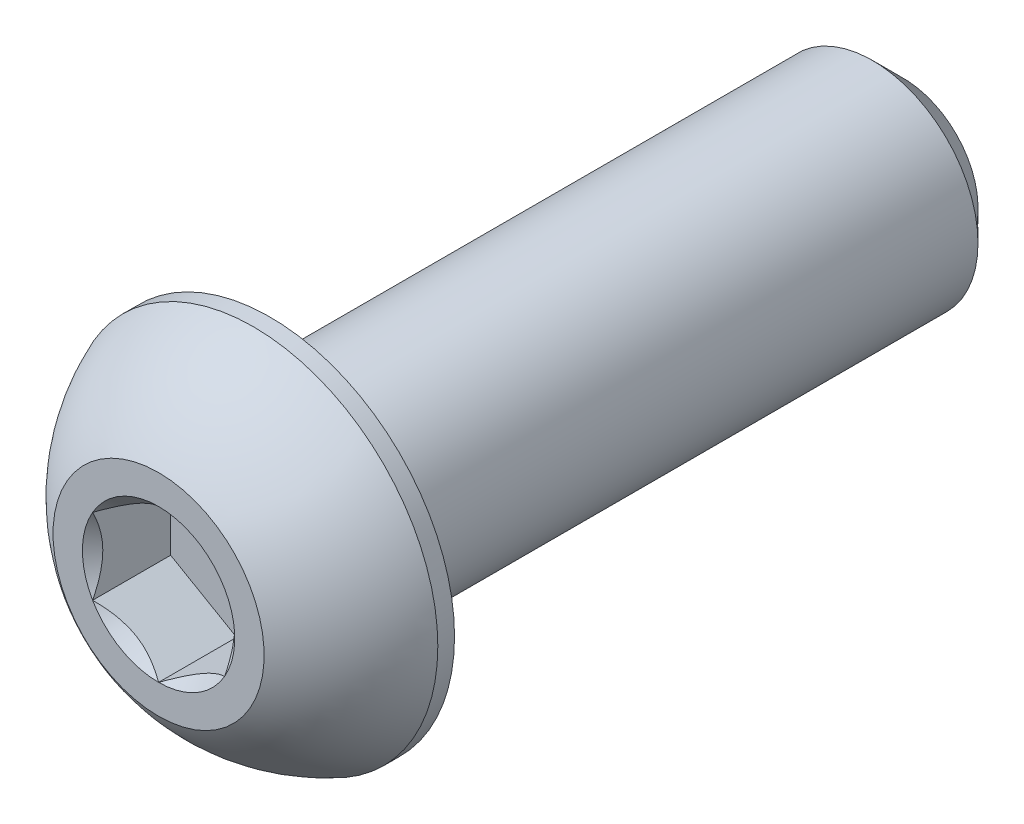
SolidWorks part; units mm, degrees
ref_plane "Front" through (0, 0, 0) normal (0, 0, 1) x (1, 0, 0)
ref_plane "Top" through (0, 0, 0) normal (0, 1, 0) x (1, 0, 0)
ref_plane "Right" through (0, 0, 0) normal (1, 0, 0) x (0, 0, -1)
sketch "Sketch1" plane through (0, 0, 0) normal (1, 0, 0) x (0, 0, -1)
  line L2 (3.3528, 3.175) -> (22.4028, 3.175)
  line L3 (22.4028, 3.175) -> (22.4028, 0)
  line L4 (22.4028, 0) -> (3.3528, 0)
  line L6 (2.8499, 5.5499) -> (3.3528, 5.5499) construction
  line L7 (22.4028, 3.175) -> (22.4028, -3.175) construction
  line L8 (0, 0) -> (3.3528, 0) construction
  line L9 (3.3528, 5.5499) -> (3.3528, -5.5499) construction
  line L11 (3.3528, 3.175) -> (3.3528, 0)
  line L13 (0, 1.9844) -> (0, -1.9844) construction
  line L14 (0, 1.9844) -> (0, 3.175) construction
  arc A3 (0, 3.175) -> (2.8499, 5.5499) centre (5.0603, 0) cw construction
  dimension "D1" = 0.5029
revolve "Revolve1" add sketch "Sketch1" angle 360 mid plane about L4
sketch "Sketch3" plane through (0, 0, -22.4028) normal (0, 0, -1) x (-1, 0, 0)
  circle A0 centre (0, 0) radius 3.175
curve "Helix/Spiral1" pitch 1.239 height 22.4028 turns 18.081
sketch "Sketch2" plane through (0, 0, 0) normal (1, 0, 0) x (0, 0, -1)
  line L0 (22.4028, 3.175) -> (23.4869, 3.175)
  line L1 (23.4869, 3.175) -> (23.0223, 2.3702)
  line L2 (23.0223, 2.3702) -> (22.8674, 2.3702)
  line L3 (22.8674, 2.3702) -> (22.4028, 3.175)
  line L4 (22.6351, 2.7726) -> (23.2546, 2.7726) construction
  dimension "D1" = 60
  dimension "D2" = 0.1549
  dimension "D3" = 0.6195
chamfer "Chamfer1" distance 0.9293 angle 45 1 edges at (0, 3.175, -22.4028)
sweep "Cut-Sweep1" [suppressed] cut profiles "Sketch2" path "Helix/Spiral1"
sketch "Sketch7" plane through (0, 0, 0) normal (1, 0, 0) x (0, 0, -1)
  line L6 (2.8499, 5.5499) -> (3.3528, 5.5499) construction
  line L8 (0, 0) -> (3.3528, 0) construction
  line L11 (3.3528, 5.5499) -> (3.3528, -5.5499) construction
  line L12 (2.8499, 5.5499) -> (3.3528, 5.5499)
  line L13 (0, 0) -> (3.3528, 0)
  line L14 (0, 1.9844) -> (0, -1.9844) construction
  line L15 (3.3528, 5.5499) -> (3.3528, 0)
  line L16 (0, 3.175) -> (0, 0)
  arc A2 (2.8499, 5.5499) -> (0, 3.175) centre (5.0603, 0) ccw construction
  arc A3 (2.8499, 5.5499) -> (0, 3.175) centre (5.0603, 0) ccw
revolve "Revolve2" add sketch "Sketch7" angle 360 mid plane about L13
sketch "Sketch5" plane through (0, 0, 0) normal (0, 0, 1) x (1, 0, 0)
  line L1 (1.9844, -1.1457) -> (1.9844, 1.1457)
  line L2 (1.9844, 1.1457) -> (0, 2.2914)
  line L3 (0, 2.2914) -> (-1.9844, 1.1457)
  line L4 (-1.9844, 1.1457) -> (-1.9844, -1.1457)
  line L5 (-1.9844, -1.1457) -> (0, -2.2914)
  line L6 (0, -2.2914) -> (1.9844, -1.1457)
  circle A0 centre (0, 0) radius 1.9844 construction
extrude "Cut-Extrude2" cut sketch "Sketch5" against normal blind 2.347
sketch "Sketch6" plane through (0, 0, 0) normal (0, 0, 1) x (1, 0, 0)
  circle A0 centre (0, 0) radius 2.2914
extrude "Cut-Extrude3" cut sketch "Sketch6" against normal blind 2.347 draft 45
sketch "Sketch9" [suppressed] plane through (0, 0, -3.3528) normal (0, 0, 1) x (1, 0, 0)
  circle A2 centre (0, 0) radius 3.175
extrude "Boss-Extrude2" [suppressed] add sketch "Sketch9" against normal offset from surface (76.2 mm away) 22.225
sketch "Sketch10" plane through (0, 0, 0) normal (1, 0, 0) x (0, 0, -1)
  line L0 (22.4028, 3.175) -> (22.4028, -3.175) construction
  point P0 (20.5443, -3.175)
  dimension "D1" = 1.8585
equation "\"D3@Helix/Spiral1\" = \"Lg@Sketch1\" + \"Head Ht@Sketch1\""
equation "\"D2@Sketch2\" = \"D4@Helix/Spiral1\" * .125"
equation "\"D3@Sketch2\" = \"D4@Helix/Spiral1\" * .5"
equation "\"D1@Chamfer1\" = \"D4@Helix/Spiral1\" * .75"
equation "\"D1@Cut-Extrude2\" = \"Head Ht@Sketch1\" * .7"
equation "\"D1@Sketch1\" = \"Head Ht@Sketch1\" * .15"
equation "\"D1@Sketch10\" = \"D4@Helix/Spiral1\" * 1.5"
equation "\"D1@Cut-Extrude3\" = \"D1@Cut-Extrude2\""
